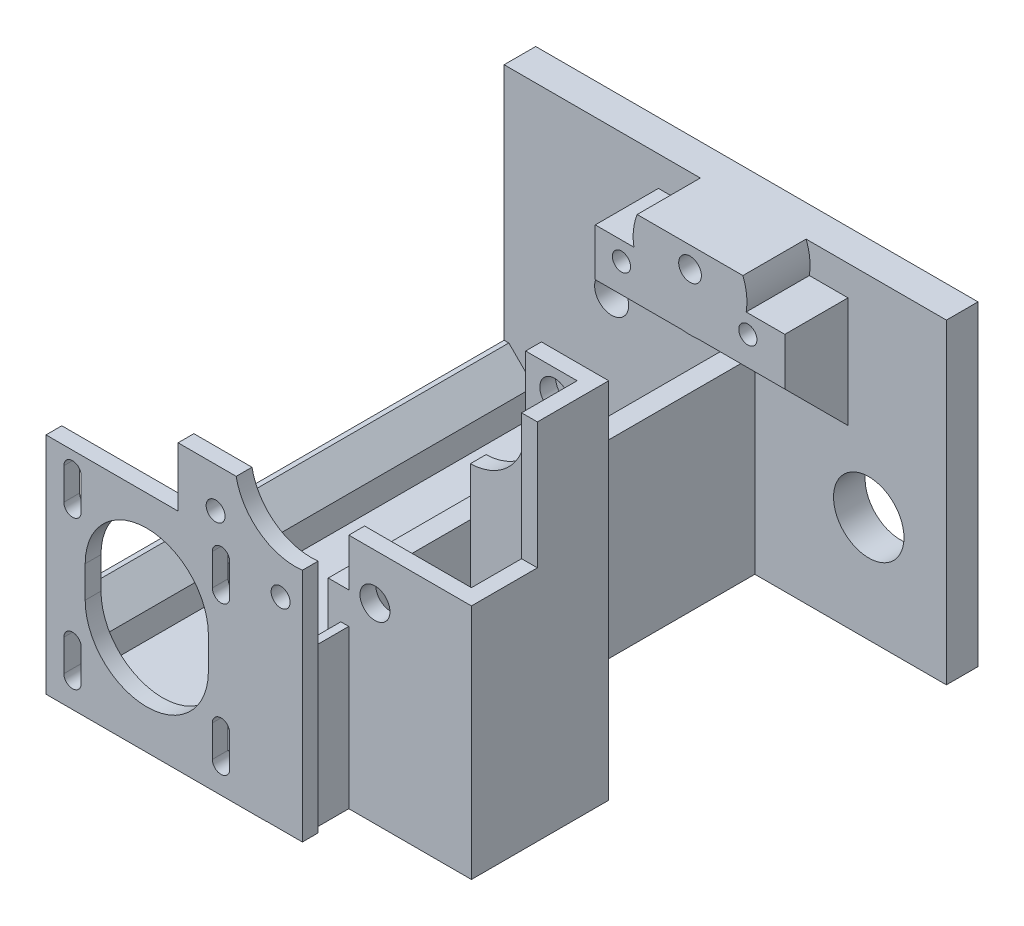
SolidWorks part; units mm, degrees
material "ABS"
ref_plane "Front Plane" through (0, 0, 0) normal (0, 0, 1) x (1, 0, 0)
ref_plane "Top Plane" through (0, 0, 0) normal (0, 1, 0) x (1, 0, 0)
ref_plane "Right Plane" through (0, 0, 0) normal (1, 0, 0) x (0, 0, -1)
sketch "Sketch1" plane through (0, 0, 0) normal (0, 0, 1) x (1, 0, 0)
  line L1 (-65.5446, 32.6733) -> (74.4554, 32.6733)
  line L2 (-65.5446, 32.6733) -> (-65.5446, -67.3267)
  line L3 (-65.5446, -67.3267) -> (74.4554, -67.3267)
  line L4 (74.4554, 32.6733) -> (74.4554, -67.3267)
  dimension "D1" = 100
  dimension "D2" = 140
extrude "Boss-Extrude1" add sketch "Sketch1" along normal blind 10
sketch "Sketch2" plane through (0, 0, 10) normal (0, 0, 1) x (1, 0, 0)
  line L0 (-65.5446, -67.3267) -> (-65.5446, -42.849)
  line L3 (-65.5446, -67.3267) -> (7.3151, -67.3267)
  line L5 (-65.5446, -67.3267) -> (74.4554, -67.3267) construction
  line L8 (-65.5446, 32.6733) -> (-65.5446, -67.3267) construction
  line L9 (-65.5446, -42.849) -> (-56.0483, -42.849)
  line L10 (-56.0483, -42.849) -> (-56.0483, -59.0904)
  line L11 (-56.0483, -59.0904) -> (7.3151, -59.0904)
  line L12 (7.3151, -59.0904) -> (7.3151, -7.3423)
  line L13 (7.3151, -7.3423) -> (13.8255, -7.3423)
  line L14 (13.8255, -7.3423) -> (13.8255, -67.3267)
  line L15 (13.8255, -67.3267) -> (7.3151, -67.3267)
extrude "Boss-Extrude2" add sketch "Sketch2" along normal blind 140
sketch "Sketch3" plane through (0, 0, 10) normal (0, 0, 1) x (1, 0, 0)
  line L1 (-16.6941, 23.1955) -> (43.3059, 23.1955)
  line L2 (-16.6941, 23.1955) -> (-16.6941, 8.1955)
  line L3 (-16.6941, 8.1955) -> (43.3059, 8.1955)
  line L4 (43.3059, 23.1955) -> (43.3059, 8.1955)
  dimension "D1" = 15
  dimension "D2" = 60
extrude "Boss-Extrude3" add sketch "Sketch3" along normal blind 20
sketch "Sketch4" plane through (0, 0, 10) normal (0, 0, 1) x (1, 0, 0)
  line L0 (43.3059, 8.1955) -> (43.3059, 23.1955) construction
  circle A0 centre (13.3059, 26.0432) radius 18
  dimension "D1" = 36
  dimension "D2" = 30
extrude "Boss-Extrude4" add sketch "Sketch4" along normal blind 20
sketch "Sketch6" plane through (0, 0, 30) normal (0, 0, 1) x (1, 0, 0)
  circle A0 centre (13.3059, 26.0432) radius 3.5973
  arc A1 (31.0792, 23.1955) -> (-4.4674, 23.1955) centre (13.3059, 26.0432) ccw construction
extrude "Cut-Extrude2" cut sketch "Sketch6" against normal blind 100
sketch "Sketch5" plane through (0, 0, 30) normal (0, 0, 1) x (1, 0, 0)
  line L0 (74.4554, 32.6733) -> (30.0404, 32.6733) construction
  line L1 (-13.303, 47.4) -> (34.4273, 47.4)
  line L2 (-13.303, 47.4) -> (-13.303, 32.6733)
  line L3 (-13.303, 32.6733) -> (34.4273, 32.6733)
  line L4 (34.4273, 47.4) -> (34.4273, 32.6733)
extrude "Cut-Extrude1" cut sketch "Sketch5" against normal blind 20
sketch "Sketch7" plane through (0, 0, 30) normal (0, 0, 1) x (1, 0, 0)
  circle A0 centre (-8.3949, 17.2978) radius 2.8779
extrude "Cut-Extrude3" cut sketch "Sketch7" against normal blind 100
pattern_linear "LPattern1" count 2 spacing 40 along (1, 0, 0) of "Cut-Extrude3"
sketch "Sketch9" plane through (0, 0, 150) normal (0, 0, 1) x (1, 0, 0)
  line L0 (-65.5446, 32.6733) -> (-65.5446, -42.849) construction
  line L1 (4.1877, 3.7072) -> (-65.5446, 3.7072)
  line L2 (4.1877, 3.7072) -> (4.1877, -67.3896)
  line L3 (4.1877, -67.3896) -> (-65.5446, -67.3896)
  line L4 (-65.5446, 3.7072) -> (-65.5446, -67.3896)
extrude "Boss-Extrude5" add sketch "Sketch9" along normal blind 5
chamfer "Chamfer1" distance 20 angle 45 2 edges at (29.4741, 8.1955, 10) (-2.8623, 8.1955, 10)
sketch "Sketch11" plane through (0, 0, 155) normal (0, 0, 1) x (1, 0, 0)
  line L0 (13.8255, -67.3267) -> (74.4554, -67.3267) construction
  line L1 (-23.7439, 22.4423) -> (15.6103, 22.4423)
  line L2 (-23.7439, 22.4423) -> (-23.7439, -67.3267)
  line L3 (-23.7439, -67.3267) -> (15.6103, -67.3267)
  line L4 (15.6103, 22.4423) -> (15.6103, -67.3267)
extrude "Boss-Extrude6" add sketch "Sketch11" against normal blind 5
sketch "Sketch12" plane through (0, 0, 155) normal (0, 0, 1) x (1, 0, 0)
  circle A0 centre (13.3059, 26.0432) radius 19
extrude "Cut-Extrude5" cut sketch "Sketch12" against normal blind 10
sketch "Sketch13" plane through (0, 0, 155) normal (0, 0, 1) x (1, 0, 0)
  circle A0 centre (-11.8599, 9.7129) radius 3
  circle A1 centre (8.7091, -3.6025) radius 3
  circle A2 centre (13.3059, 26.0432) radius 30 construction
  point P7 (9.9688, 4.5216)
  point P8 (-4.9635, 14.188)
  dimension "D1" = 6
  dimension "D2" = 6
extrude "Cut-Extrude6" cut sketch "Sketch13" against normal blind 10
fillet "Fillet2" radius 10 rebuild error yes
chamfer "Chamfer2" distance 8 angle 45 1 edges at (-56.0483, -42.849, 80)
sketch "Sketch14" plane through (0, 0, 10) normal (0, 0, 1) x (1, 0, 0)
  circle A0 centre (-31.5077, -13.6101) radius 5.3914
  circle A1 centre (49.8779, -33.6888) radius 11.1548
extrude "Cut-Extrude7" cut sketch "Sketch14" against normal blind 10
sketch "Sketch15" plane through (0, -67.3267, 0) normal (0, -1, 0) x (1, 0, 0)
  line L1 (4.5956, 95.0738) -> (52.6384, 95.0738)
  line L2 (4.5956, 95.0738) -> (4.5956, 138.5253)
  line L3 (4.5956, 138.5253) -> (52.6384, 138.5253)
  line L4 (52.6384, 95.0738) -> (52.6384, 138.5253)
extrude "Boss-Extrude7" add sketch "Sketch15" against normal blind 5
sketch "Sketch16" plane through (0, -62.3267, 0) normal (0, 1, 0) x (1, 0, 0)
  line L8 (13.8255, -133.5253) -> (13.8255, -138.5253)
  line L9 (13.8255, -138.5253) -> (13.8255, -95.0738) construction
  line L10 (13.8255, -138.5253) -> (52.6384, -138.5253)
  line L11 (52.6384, -138.5253) -> (52.6384, -116.7995)
  line L12 (52.6384, -95.0738) -> (52.6384, -138.5253) construction
  line L13 (52.6384, -116.7995) -> (47.6384, -116.7995)
  line L14 (47.6384, -116.7995) -> (47.6384, -133.5253)
  line L15 (47.6384, -133.5253) -> (13.8255, -133.5253)
  dimension "D1" = 5
  dimension "D2" = 5
extrude "Boss-Extrude8" add sketch "Sketch16" along normal blind 70
sketch "Sketch17" plane through (0, 7.6733, 0) normal (0, 1, 0) x (1, 0, 0)
  line L1 (28.8586, -179.0031) -> (38.4745, -179.0031)
  line L2 (28.8586, -179.0031) -> (28.8586, -197.9959)
  line L3 (28.8586, -197.9959) -> (38.4745, -197.9959)
  line L4 (38.4745, -179.0031) -> (38.4745, -197.9959)
extrude "Cut-Extrude8" cut sketch "Sketch17" against normal blind 20 rebuild error yes
sketch "Sketch18" plane through (0, 0, 138.5253) normal (0, 0, 1) x (1, 0, 0)
  circle A0 centre (22.1124, -6.8448) radius 4.75
  dimension "D1" = 9.5
extrude "Cut-Extrude9" cut sketch "Sketch18" against normal blind 20
sketch "Sketch19" plane through (0, -62.3267, 0) normal (0, 1, 0) x (1, 0, 0)
  line L0 (13.8199, -95.0738) -> (13.8199, -100.0738)
  line L3 (13.8199, -100.0738) -> (47.6384, -100.0738)
  line L6 (47.6384, -100.0738) -> (47.6384, -117.6475)
  line L7 (47.6384, -117.6475) -> (52.6384, -117.6475)
  line L8 (52.6384, -95.0738) -> (52.6384, -116.7995) construction
  line L9 (52.6384, -117.6475) -> (52.6384, -95.0738)
  line L10 (52.6384, -95.0738) -> (13.8199, -95.0738)
  dimension "D1" = 5
  dimension "D2" = 5
extrude "Boss-Extrude9" add sketch "Sketch19" along normal blind 110
sketch "Sketch20" plane through (0, 0, 100.0738) normal (0, 0, 1) x (1, 0, 0)
  line L0 (13.3059, 26.0432) -> (13.3059, 51.1413) construction
  line L1 (-4.7235, 26.0432) -> (-4.7235, 51.1413)
  line L2 (31.3354, 26.0432) -> (31.3354, 51.1413)
  arc A0 (-4.7235, 26.0432) -> (31.3354, 26.0432) centre (13.3059, 26.0432) ccw
  arc A1 (31.3354, 51.1413) -> (-4.7235, 51.1413) centre (13.3059, 51.1413) ccw
  point P3 (13.3059, 38.5923)
extrude "Cut-Extrude10" cut sketch "Sketch20" against normal blind 70
sketch "Sketch21" plane through (0, 0, 100.0738) normal (0, 0, 1) x (1, 0, 0)
  circle A0 centre (40.582, 40.031) radius 4.75
  dimension "D1" = 9.5
extrude "Cut-Extrude11" cut sketch "Sketch21" against normal blind 70
sketch "Sketch22" plane through (0, 0, 155) normal (0, 0, 1) x (1, 0, 0)
  line L0 (-57.1445, -58.9171) -> (-57.1445, -48.9171) construction
  line L1 (-59.8916, -58.9171) -> (-59.8916, -48.9171)
  line L2 (-54.3974, -58.9171) -> (-54.3974, -48.9171)
  line L3 (-33.6445, -35.4171) -> (-33.6445, -25.4171) construction
  line L4 (-53.1445, -35.4171) -> (-53.1445, -25.4171)
  line L5 (-14.1445, -35.4171) -> (-14.1445, -25.4171)
  line L6 (-10.1445, -58.9171) -> (-10.1445, -48.9171) construction
  line L7 (-12.8916, -58.9171) -> (-12.8916, -48.9171)
  line L8 (-7.3974, -58.9171) -> (-7.3974, -48.9171)
  line L9 (-10.1445, -11.9171) -> (-10.1445, -1.9171) construction
  line L10 (-12.8916, -11.9171) -> (-12.8916, -1.9171)
  line L11 (-7.3974, -11.9171) -> (-7.3974, -1.9171)
  line L12 (-57.1445, -11.9171) -> (-57.1445, -1.9171) construction
  line L13 (-59.8916, -11.9171) -> (-59.8916, -1.9171)
  line L14 (-54.3974, -11.9171) -> (-54.3974, -1.9171)
  arc A0 (-59.8916, -58.9171) -> (-54.3974, -58.9171) centre (-57.1445, -58.9171) ccw
  arc A1 (-54.3974, -48.9171) -> (-59.8916, -48.9171) centre (-57.1445, -48.9171) ccw
  arc A2 (-53.1445, -35.4171) -> (-14.1445, -35.4171) centre (-33.6445, -35.4171) ccw
  arc A3 (-14.1445, -25.4171) -> (-53.1445, -25.4171) centre (-33.6445, -25.4171) ccw
  arc A4 (-12.8916, -58.9171) -> (-7.3974, -58.9171) centre (-10.1445, -58.9171) ccw
  arc A5 (-7.3974, -48.9171) -> (-12.8916, -48.9171) centre (-10.1445, -48.9171) ccw
  arc A6 (-12.8916, -11.9171) -> (-7.3974, -11.9171) centre (-10.1445, -11.9171) ccw
  arc A7 (-7.3974, -1.9171) -> (-12.8916, -1.9171) centre (-10.1445, -1.9171) ccw
  arc A8 (-59.8916, -11.9171) -> (-54.3974, -11.9171) centre (-57.1445, -11.9171) ccw
  arc A9 (-54.3974, -1.9171) -> (-59.8916, -1.9171) centre (-57.1445, -1.9171) ccw
  point P2 (-57.1445, -53.9171)
  point P9 (-33.6445, -30.4171)
  point P16 (-10.1445, -53.9171)
  point P23 (-10.1445, -6.9171)
  point P30 (-57.1445, -6.9171)
  dimension "D5" = 19.5
  dimension "D1" = 10
  dimension "D2" = 10
  dimension "D3" = 23.5
  dimension "D4" = 23.5
extrude "Cut-Extrude12" cut sketch "Sketch22" against normal blind 10
sketch "Sketch23" plane through (7.3151, 0, 0) normal (-1, 0, 0) x (0, 0, 1)
  line L0 (150, 3.7072) -> (150, -42.849) construction
  line L1 (138.5253, -7.3423) -> (150, -7.3423)
  line L2 (138.5253, -7.3423) -> (138.5253, -17.3423)
  line L3 (138.5253, -17.3423) -> (150, -17.3423)
  line L4 (150, -7.3423) -> (150, -17.3423)
  dimension "D1" = 10
extrude "Cut-Extrude13" cut sketch "Sketch23" against normal blind 10
chamfer "Chamfer4" distance 4 angle 45 1 edges at (7.3151, -17.3423, 144.2627)
